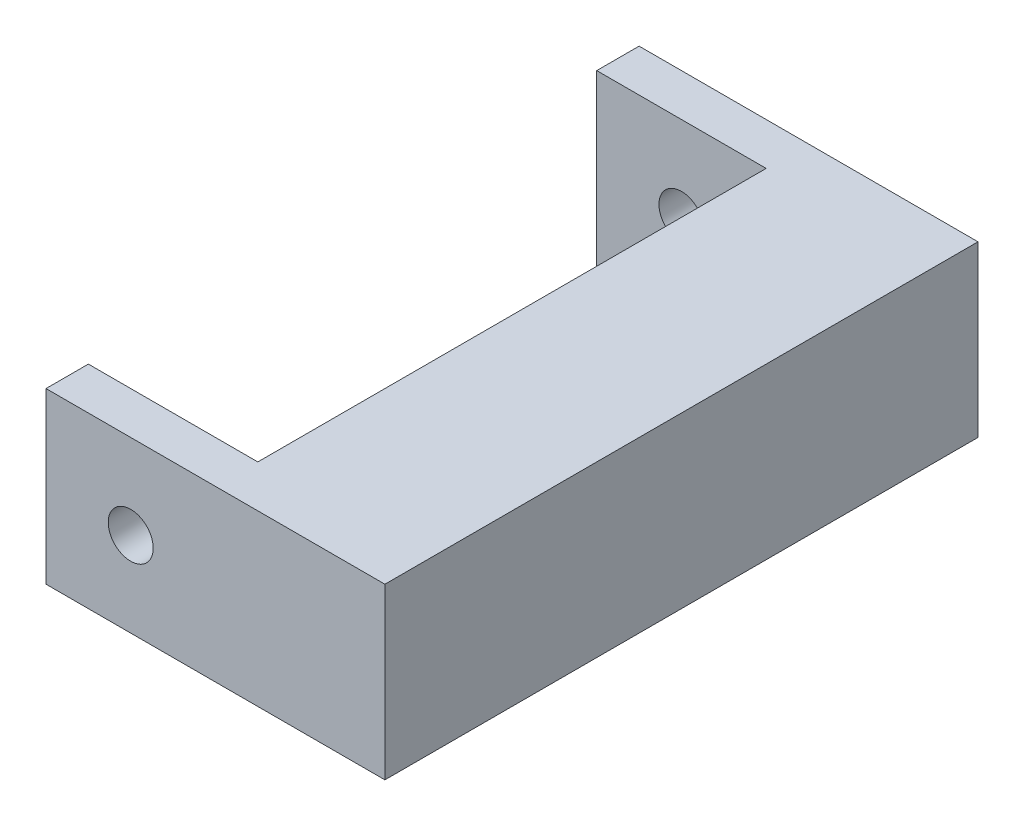
SolidWorks part; units mm, degrees
ref_plane "Front Plane" through (0, 0, 0) normal (0, 0, 1) x (1, 0, 0)
ref_plane "Top Plane" through (0, 0, 0) normal (0, 1, 0) x (1, 0, 0)
ref_plane "Right Plane" through (0, 0, 0) normal (1, 0, 0) x (0, 0, -1)
sketch "Sketch2" plane through (0, 0, 0) normal (0, 0, 1) x (1, 0, 0)
  line L1 (-10, 10) -> (10, 10)
  line L2 (-10, 10) -> (-10, -10)
  line L3 (-10, -10) -> (10, -10)
  line L4 (10, 10) -> (10, -10)
  line L5 (-10, 10) -> (10, -10) construction
  line L6 (-10, -10) -> (10, 10) construction
  line L7 (10, 10) -> (30, 10)
  line L8 (10, 10) -> (10, -10)
  line L9 (10, -10) -> (30, -10)
  line L10 (30, 10) -> (30, -10)
  circle A0 centre (0, 0) radius 2.655
  point P0 (0, 0)
  dimension "D3" = 5.31
  dimension "D1" = 20
  dimension "D2" = 20
  dimension "D4" = 20
extrude "Boss-Extrude1" add sketch "Sketch2" along normal blind 5 contours L4 L1 L2 L3 A0 region at (0, 9.7172, 0)
extrude "Boss-Extrude2" add sketch "Sketch2<3>" along normal blind 70 contours L10 L7 L4 L9 region at (20, 0, 0)
sketch "Sketch2<3>" plane through (0, 0, 0) normal (0, 0, 1) x (1, 0, 0) same geometry as "Sketch2"
extrude "Boss-Extrude3" add sketch "Sketch2<4>" against normal blind 5 from surface contours L4 L1 L2 L3 A0 region at (0, 9.7172, 0) starting at face at (20, 0, 70)
sketch "Sketch2<4>" plane through (0, 0, 0) normal (0, 0, 1) x (1, 0, 0) same geometry as "Sketch2"
